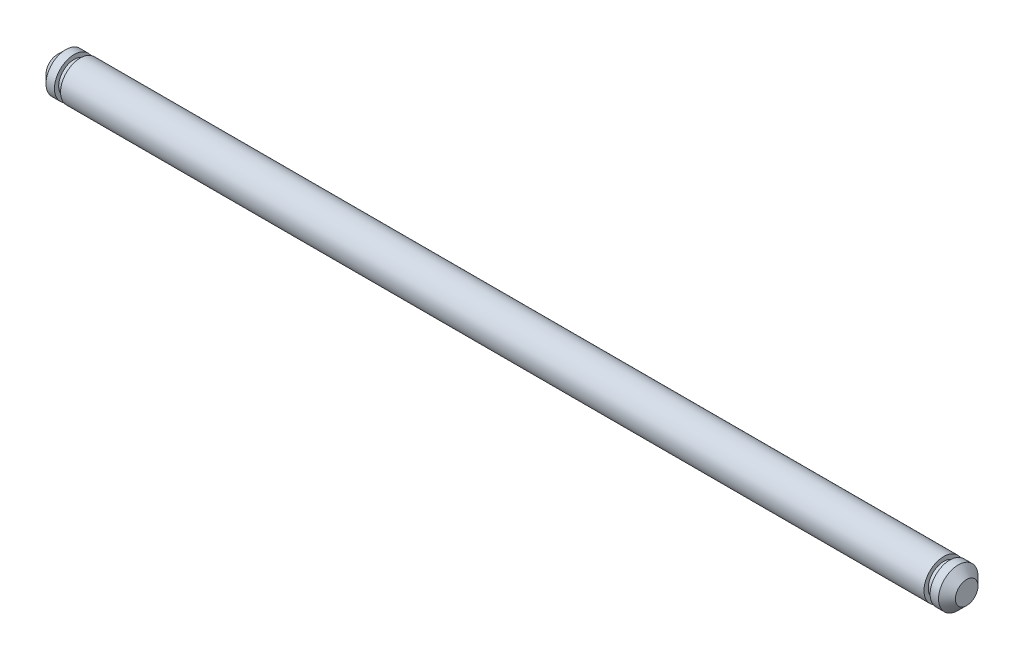
SolidWorks part; units mm, degrees
material "AISI 1020"
ref_plane "Front" through (0, 0, 0) normal (0, 0, 1) x (1, 0, 0)
ref_plane "Top" through (0, 0, 0) normal (0, 1, 0) x (1, 0, 0)
ref_plane "Right" through (0, 0, 0) normal (1, 0, 0) x (0, 0, -1)
ref_axis "side-side" through (80.9, 0, 0) along (-1, 0, 0)
ref_axis "up-down" through (0, 50, 0) along (0, -1, 0)
ref_axis "front-back" through (0, 0, -80.9) along (0, 0, 1)
sketch "Sketch2" plane through (0, 0, 0) normal (0, 0, 1) x (1, 0, 0)
  line L0 (0, 0) -> (-65.1401, 0) construction
  line L1 (0, 2.3812) -> (104.14, 2.3812)
  line L2 (-2.7686, 0) -> (106.9086, 0)
  line L3 (-2.7686, 0) -> (-2.7686, 2.3813)
  line L4 (-2.7686, 2.3813) -> (-0.7366, 2.3812)
  line L5 (106.9086, 0) -> (106.9086, 2.3812)
  line L7 (-0.7366, 2.3812) -> (-0.7366, 1.8669)
  line L8 (-0.7366, 1.8669) -> (0, 1.8669)
  line L9 (0, 2.3812) -> (0, 1.8669)
  line L10 (104.8766, 2.3812) -> (106.9086, 2.3812)
  line L12 (104.14, 2.3812) -> (104.14, 1.8669)
  line L13 (104.14, 1.8669) -> (104.8766, 1.8669)
  line L14 (104.8766, 2.3812) -> (104.8766, 1.8669)
  dimension "D1" = 0.7366
  dimension "D2" = 3.7338
  dimension "D3" = 4.7625
  dimension "D4" = 2.032
  dimension "D5" = 104.14
  dimension "D6" = 0.5143
revolve "Revolve1" add sketch "Sketch2" angle 360 about L0
chamfer "Chamfer1" distance 1.016 angle 45 2 edges at (-2.7686, 0, -2.3813) (106.9086, 0, -2.3812)
